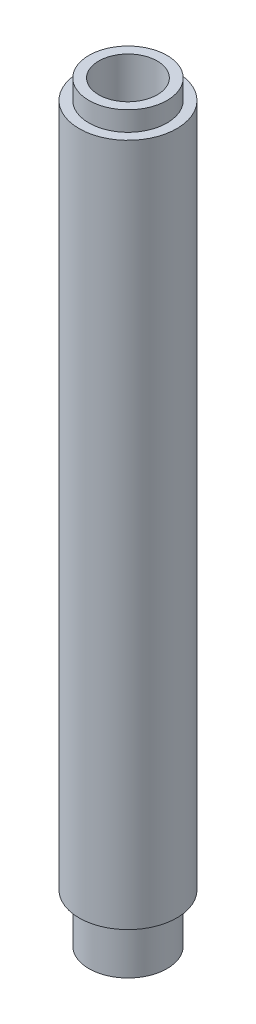
SolidWorks part; units mm, degrees
ref_plane "Front Plane" through (0, 0, 0) normal (0, 0, 1) x (1, 0, 0)
ref_plane "Top Plane" through (0, 0, 0) normal (0, 1, 0) x (1, 0, 0)
ref_plane "Right Plane" through (0, 0, 0) normal (1, 0, 0) x (0, 0, -1)
sketch "Sketch1" plane through (0, 0, 0) normal (0, 1, 0) x (1, 0, 0)
  circle A0 centre (0, 0) radius 12.7
  dimension "D1" = 25.4
extrude "Boss-Extrude1" add sketch "Sketch1" along normal blind 177.8
sketch "Sketch4" plane through (0, 177.8, 0) normal (0, 1, 0) x (1, 0, 0)
  circle A2 centre (0, 0) radius 10.16
  circle A3 centre (0, 0) radius 10.16
  dimension "D1" = 2.54
extrude "Boss-Extrude2" add sketch "Sketch4" along normal blind 5.08
sketch "Sketch5" plane through (0, 182.88, 0) normal (0, 1, 0) x (1, 0, 0)
  circle A0 centre (0, 0) radius 10.16 construction
  circle A1 centre (0, 0) radius 10.16 construction
  circle A2 centre (0, 0) radius 7.62
  dimension "D1" = 2.54
extrude "Cut-Extrude1" cut sketch "Sketch5" against normal through all
sketch "Sketch6" plane through (0, 0, 0) normal (0, -1, 0) x (1, 0, 0)
  circle A0 centre (0, 0) radius 10.16
  circle A1 centre (0, 0) radius 7.62 construction
  circle A2 centre (0, 0) radius 7.62
  dimension "D1" = 20.32
extrude "Boss-Extrude3" add sketch "Sketch6" along normal blind 12.7
sketch "Sketch7" plane through (0, -12.7, 0) normal (0, -1, 0) x (1, 0, 0)
  circle A0 centre (0, 0) radius 12.7 construction
  circle A1 centre (0, 0) radius 12.7
sketch "Sketch8" plane through (0, 182.88, 0) normal (0, 1, 0) x (1, 0, 0)
  circle A0 centre (0, 0) radius 12.7 construction
  circle A1 centre (0, 0) radius 12.7
